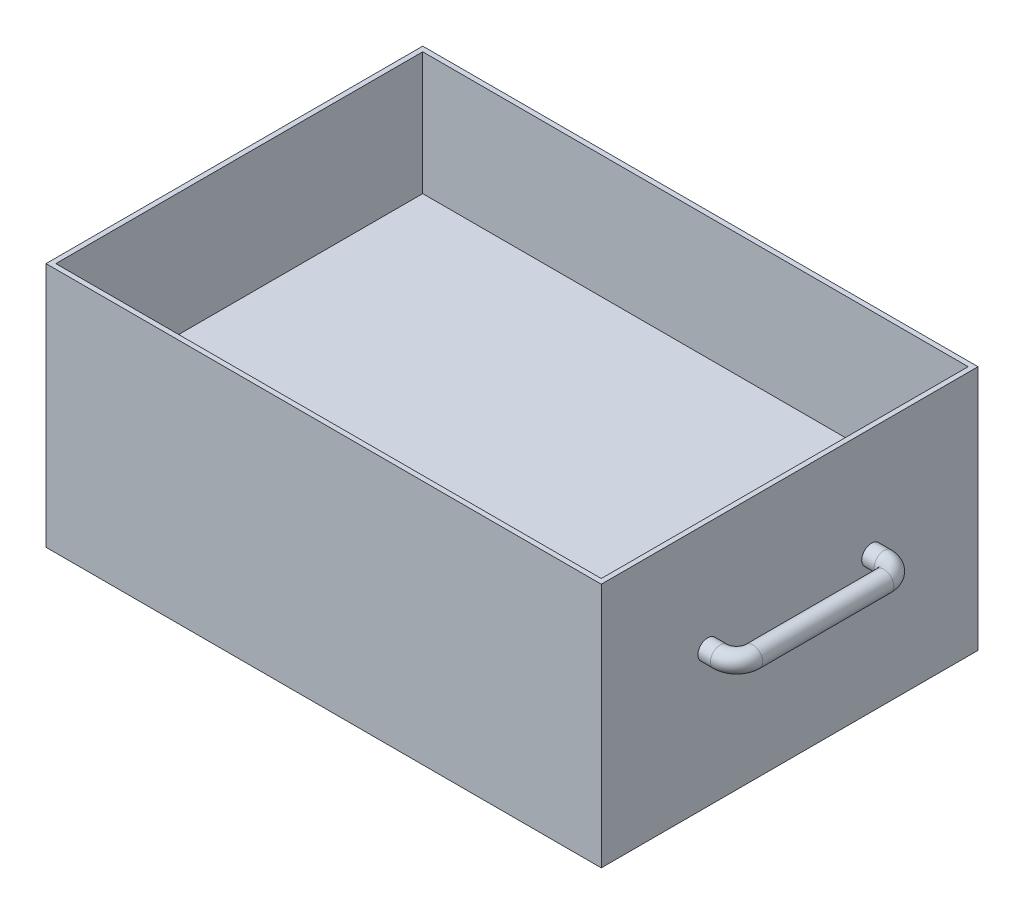
SolidWorks part; units mm, degrees
ref_plane "前视" through (0, 0, 0) normal (0, 0, 1) x (1, 0, 0)
ref_plane "上视" through (0, 0, 0) normal (0, 1, 0) x (1, 0, 0)
ref_plane "右视" through (0, 0, 0) normal (1, 0, 0) x (0, 0, -1)
sketch "Sketch1" plane through (0, 0, 0) normal (0, 1, 0) x (1, 0, 0)
  line L1 (-161.8201, 119.8745) -> (177.1799, 119.8745)
  line L2 (-161.8201, 119.8745) -> (-161.8201, -110.1255)
  line L3 (-161.8201, -110.1255) -> (177.1799, -110.1255)
  line L4 (177.1799, 119.8745) -> (177.1799, -110.1255)
  dimension "D1" = 339
  dimension "D2" = 230
  dimension "D3" = 177.1799
extrude "Boss-Extrude1" add sketch "Sketch1" along normal blind 150
shell "Shell1" thickness 3 removed face at (7.6799, 150, -4.8745)
shell "Shell2" thickness 3 removed face at (7.6799, 0, -4.8745)
sketch "Sketch2" plane through (177.1799, 0, 0) normal (1, 0, 0) x (0, 0, -1)
  line L1 (-110.1255, 150) -> (-110.1255, 0) construction
  circle A0 centre (-45.1255, 83.1724) radius 6
  point P9 (54.8745, 83.1724)
  dimension "D2" = 65
ref_plane "Plane1" through (0, 83.1724, 0) normal (0, 1, 0) x (1, 0, 0)
sketch "Sketch4" plane through (0, 83.1724, 0) normal (0, 1, 0) x (1, 0, 0)
  line L0 (177.1799, -45.1255) -> (184.7899, -45.1255)
  line L1 (194.7899, -35.1255) -> (194.7899, 44.8745)
  line L2 (184.7899, 54.8745) -> (177.1799, 54.8745)
  arc A0 (194.7899, -35.1255) -> (184.7899, -45.1255) centre (184.7899, -35.1255) cw
  arc A1 (194.7899, 44.8745) -> (184.7899, 54.8745) centre (184.7899, 44.8745) ccw
  dimension "D1" = 10
sweep "Sweep2" add profiles "Sketch2" path "Sketch4"
